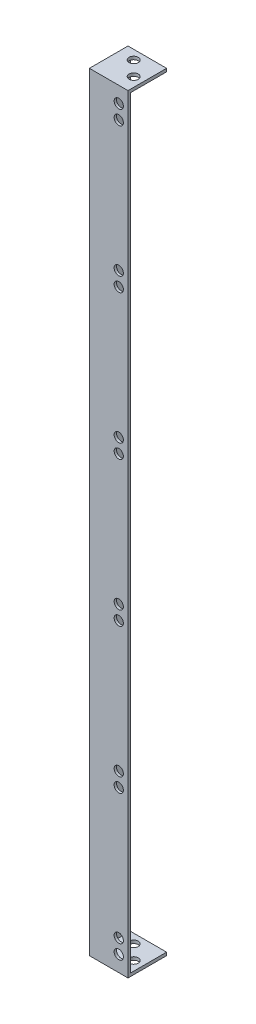
SolidWorks part; units mm, degrees
ref_plane "Front Plane" through (0, 0, 0) normal (0, 0, 1) x (1, 0, 0)
ref_plane "Top Plane" through (0, 0, 0) normal (0, 1, 0) x (1, 0, 0)
ref_plane "Right Plane" through (0, 0, 0) normal (1, 0, 0) x (0, 0, -1)
sketch "Sketch1" plane through (0, 0, 0) normal (0, 1, 0) x (1, 0, 0)
  line L0 (0, 0) -> (0, 16.3)
  line L1 (0, 16.3) -> (1, 16.3)
  line L2 (1, 16.3) -> (1, 1)
  line L3 (1, 1) -> (16.3, 1)
  line L4 (16.3, 1) -> (16.3, 0)
  line L5 (16.3, 0) -> (0, 0)
  dimension "D1" = 16.3
  dimension "D2" = 16.3
  dimension "D3" = 1
  dimension "D4" = 1
extrude "Boss-Extrude1" add sketch "Sketch1" along normal blind 327 contours L0 L1 L2 L3 L4 L5
sketch "Sketch2" plane through (0, 0, 0) normal (0, 0, 1) x (1, 0, 0)
  line L0 (16.3, 327) -> (16.3, 0) construction
  line L1 (16.3, 327) -> (0, 327) construction
  circle A0 centre (12.4, 319) radius 1.95
  circle A1 centre (12.4, 313) radius 1.95
  circle A2 centre (12.4, 258) radius 1.95
  circle A3 centre (12.4, 252) radius 1.95
  circle A4 centre (12.4, 197) radius 1.95
  circle A5 centre (12.4, 191) radius 1.95
  circle A6 centre (12.4, 136) radius 1.95
  circle A7 centre (12.4, 130) radius 1.95
  circle A8 centre (12.4, 75) radius 1.95
  circle A9 centre (12.4, 69) radius 1.95
  circle A10 centre (12.4, 14) radius 1.95
  circle A11 centre (12.4, 8) radius 1.95
  dimension "D1" = 3.9
  dimension "D2" = 3.9
  dimension "D3" = 3.9
  dimension "D4" = 3.9
  dimension "D5" = 6
  dimension "D6" = 8
  dimension "D7" = 6
extrude "Cut-Extrude1" cut sketch "Sketch2" against normal blind 2 contours A4 | A5 | A6 | A7 | A8 | A9 | A10 | A11 | A0 | A1 | A2 | A3 region at (12.4, 197, 0) region at (12.4, 191, 0) region at (12.4, 136, 0) region at (12.4, 130, 0) region at (12.4, 75, 0) region at (12.4, 69, 0) region at (12.4, 14, 0) region at (12.4, 8, 0)
sketch "Sketch3" plane through (0, 0, 0) normal (-1, 0, 0) x (0, 0, 1)
  line L0 (-16.3, 327) -> (-16.3, 0) construction
  line L1 (0, 327) -> (-16.3, 327) construction
  circle A0 centre (-12.4, 319) radius 1.95
  circle A1 centre (-12.4, 313) radius 1.95
  circle A2 centre (-12.4, 258) radius 1.95
  circle A3 centre (-12.4, 252) radius 1.95
  circle A4 centre (-12.4, 197) radius 1.95
  circle A5 centre (-12.4, 191) radius 1.95
  circle A6 centre (-12.4, 136) radius 1.95
  circle A7 centre (-12.4, 130) radius 1.95
  circle A8 centre (-12.4, 75) radius 1.95
  circle A9 centre (-12.4, 69) radius 1.95
  circle A10 centre (-12.4, 14) radius 1.95
  circle A11 centre (-12.4, 8) radius 1.95
  dimension "D1" = 3.9
  dimension "D2" = 3.9
  dimension "D3" = 6
  dimension "D4" = 0
  dimension "D5" = 3.9
  dimension "D6" = 8
  dimension "D7" = 6
extrude "Cut-Extrude2" cut sketch "Sketch3" against normal blind 2 contours A1 | A2 | A3 | A4 | A5 | A6 | A7 | A8 | A9 | A11 | A10 | A0 region at (0, 313, -12.4) region at (0, 258, -12.4) region at (0, 252, -12.4) region at (0, 197, -12.4) region at (0, 191, -12.4) region at (0, 136, -12.4) region at (0, 130, -12.4) region at (0, 75, -12.4) region at (0, 69, -12.4) region at (0, 14, -12.4) region at (0, 8, -12.4)
sketch "Sketch5" plane through (0, 0, 0) normal (-1, 0, 0) x (0, 0, 1)
  line L0 (0, 327) -> (0, 0) construction
  line L1 (-16.3, 327) -> (0, 327)
  line L2 (-16.3, 327) -> (-16.3, 325.7)
  line L3 (-16.3, 325.7) -> (0, 325.7)
  line L4 (0, 327) -> (0, 325.7)
  line L5 (-16.3, 327) -> (-16.3, 0) construction
  line L6 (-16.3, 0) -> (0, 0)
  line L7 (-16.3, 0) -> (-16.3, 1.3)
  line L8 (-16.3, 1.3) -> (0, 1.3)
  line L9 (0, 0) -> (0, 1.3)
  line L10 (0, 0) -> (-16.3, 0) construction
  line M17 (-16.3, 0) -> (0, 0)
  line M18 (0, 0) -> (0, 327)
  line M20 (-16.3, 327) -> (-16.3, 0)
  dimension "D1" = 1.3
  dimension "D2" = 1.3
extrude "Cut-Extrude4" cut sketch "Sketch5" against normal blind 20 contours L8 M20 M17 M18 | L1 L4 L3 L2 region at (0, 0.65, -8.15)
sketch "Sketch6" plane through (0, 325.7, 0) normal (0, 1, 0) x (1, 0, 0)
  line L1 (0, 16.3) -> (16.3, 16.3)
  line L2 (0, 16.3) -> (0, 0)
  line L3 (0, 0) -> (16.3, 0)
  line L4 (16.3, 16.3) -> (16.3, 0)
extrude "Boss-Extrude3" add sketch "Sketch6" against normal blind 1.3
sketch "Sketch7" plane through (0, 1.3, 0) normal (0, -1, 0) x (1, 0, 0)
  line L1 (0, -16.3) -> (16.3, -16.3)
  line L2 (0, -16.3) -> (0, 0)
  line L3 (0, 0) -> (16.3, 0)
  line L4 (16.3, -16.3) -> (16.3, 0)
extrude "Boss-Extrude4" add sketch "Sketch7" against normal blind 1.3
sketch "Sketch8" plane through (0, 1.3, 0) normal (0, -1, 0) x (1, 0, 0)
  line L0 (16.3, 0) -> (0, 0) construction
  line L1 (0, -16.3) -> (0, 0) construction
  line L2 (16.3, -16.3) -> (0, -16.3) construction
  line L3 (16.3, 0) -> (16.3, -16.3) construction
  circle A0 centre (12.4, -6.3) radius 1.95
  circle A1 centre (6.3, -12.4) radius 1.95
  dimension "D1" = 3.9
  dimension "D2" = 3.9
  dimension "D3" = 6.3
  dimension "D4" = 6.3
  dimension "D5" = 3.9
  dimension "D6" = 3.9
extrude "Cut-Extrude7" cut sketch "Sketch8" against normal blind 350
